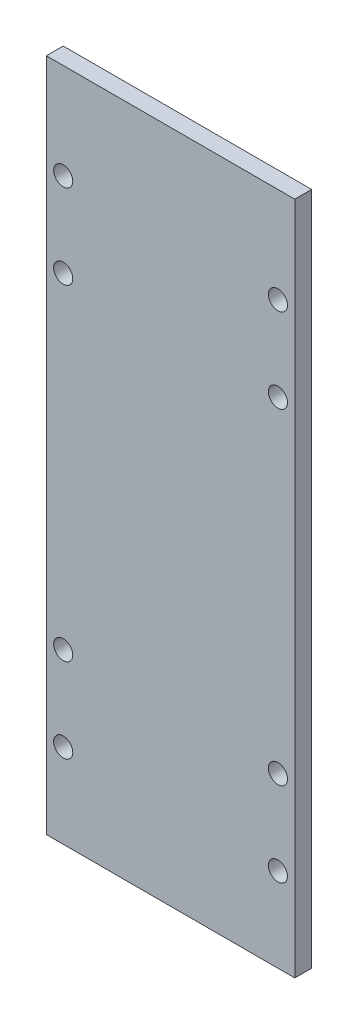
SolidWorks part; units mm, degrees
ref_plane "Front Plane" through (0, 0, 0) normal (0, 0, 1) x (1, 0, 0)
ref_plane "Top Plane" through (0, 0, 0) normal (0, 1, 0) x (1, 0, 0)
ref_plane "Right Plane" through (0, 0, 0) normal (1, 0, 0) x (0, 0, -1)
sketch "d" plane through (0, 0, 0) normal (0, 0, 1) x (1, 0, 0)
  line L1 (-21.7876, 70.4698) -> (22.4124, 70.4698)
  line L2 (-21.7876, 70.4698) -> (-21.7876, -49.5302)
  line L3 (-21.7876, -49.5302) -> (22.4124, -49.5302)
  line L4 (22.4124, 70.4698) -> (22.4124, -49.5302)
  dimension "D1" = 44.2
  dimension "D2" = 120
extrude "Boss-Extrude1" add sketch "d" along normal blind 3
sketch "Sketch4" plane through (0, 0, 3) normal (0, 0, 1) x (1, 0, 0)
  line L0 (0.3124, -49.5302) -> (0.3124, 98.4185) construction
  line L1 (-21.7876, -49.5302) -> (22.4124, -49.5302) construction
  point P0 (-18.7876, 53.4698)
  point P3 (-18.7876, 38.4698)
  point P6 (-18.7876, -19.5302)
  point P9 (-18.7876, -34.5302)
  point P20 (19.4124, -34.5302)
  point P21 (19.4124, -19.5302)
  point P22 (19.4124, 38.4698)
  point P23 (19.4124, 53.4698)
hole_wizard "M3 Clearance Hole1" positions "Sketch4" profile "Sketch5" hole size "M3" standard "DIN"
sketch "Sketch5" plane through (-18.7876, 53.4698, 3) normal (1, 0, 0) x (0, -1, 0)
  line L0 (0, 0) -> (0, 16.0215)
  line L1 (0, 16.0215) -> (1.7, 15)
  line L2 (1.7, 15) -> (1.7, 0)
  line L5 (1.7, 0) -> (0, 0)
  line L10 (0, 16.0215) -> (-1.7, 15) construction
  line L11 (0, -6.35) -> (0, 107.95) construction
  dimension "Hole Dia." = 3.4
  dimension "Hole Depth" = 15
  dimension "Drill Angle" = 118
sketch "Sketch6" [suppressed] plane through (0, 0, 3) normal (0, 0, 1) x (1, 0, 0)
  line L5 (-21.7876, 70.4698) -> (-21.7876, -49.5302) construction
  line L6 (-21.7876, 24.9698) -> (-13.7876, 24.9698)
  line L7 (-21.7876, 24.9698) -> (-21.7876, -6.0302)
  line L8 (-21.7876, -6.0302) -> (-13.7876, -6.0302)
  line L9 (-13.7876, 24.9698) -> (-13.7876, -6.0302)
  line L10 (22.4124, 70.4698) -> (-21.7876, 70.4698) construction
  dimension "D1" = 31
  dimension "D2" = 8
  dimension "D3" = 45.5
extrude "Cut-Extrude1" [suppressed] cut sketch "Sketch6" against normal through all
fillet "Fillet1" [suppressed] radius 2
